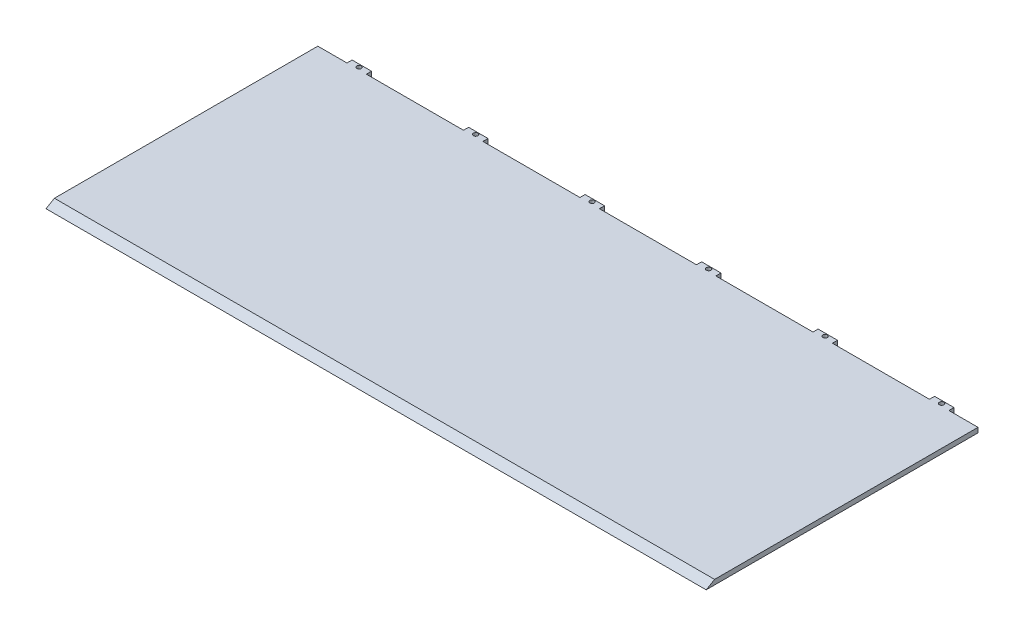
SolidWorks part; units mm, degrees
ref_plane "Front Plane" through (0, 0, 0) normal (0, 0, 1) x (1, 0, 0)
ref_plane "Top Plane" through (0, 0, 0) normal (0, 1, 0) x (1, 0, 0)
ref_plane "Right Plane" through (0, 0, 0) normal (1, 0, 0) x (0, 0, -1)
sketch "Sketch1" plane through (0, 0, 0) normal (0, 1, 0) x (1, 0, 0)
  line L1 (0, 0) -> (431.8, 0)
  line L2 (0, 0) -> (0, 177.8)
  line L3 (0, 177.8) -> (431.8, 177.8)
  line L4 (431.8, 0) -> (431.8, 177.8)
  dimension "D1" = 431.8
  dimension "D2" = 177.8
extrude "Boss-Extrude1" add sketch "Sketch1" along normal blind 3.175
sketch "Sketch2" plane through (0, 3.175, 0) normal (0, 1, 0) x (1, 0, 0)
  line L0 (431.8, 177.8) -> (0, 177.8) construction
  line L1 (19.05, 177.8) -> (31.75, 177.8)
  line L2 (19.05, 177.8) -> (19.05, 181.1655)
  line L3 (19.05, 181.1655) -> (31.75, 181.1655)
  line L4 (31.75, 177.8) -> (31.75, 181.1655)
  line L5 (0, 177.8) -> (0, 0) construction
  dimension "D1" = 12.7
  dimension "D2" = 3.3655
  dimension "D3" = 19.05
extrude "Boss-Extrude2" add sketch "Sketch2" against normal blind 3.175
hole_wizard "#32 (0.116) Diameter Hole1" positions "Sketch5" profile "Sketch4" hole size "#32" standard "ANSI Inch" end condition through all
sketch "Sketch5" plane through (0, 3.175, 0) normal (0, 1, 0) x (1, 0, 0)
  line L0 (31.75, 181.1655) -> (19.05, 181.1655) construction
  point P0 (25.4153, 179.3875)
  dimension "D1" = 1.778
sketch "Sketch4" plane through (25.4153, 3.175, -179.3875) normal (1, 0, 0) x (0, 0, 1)
  line L0 (0, 0) -> (0, 3.175)
  line L1 (0, 3.175) -> (1.4732, 3.175)
  line L2 (1.4732, 3.175) -> (1.4732, 0)
  line L5 (1.4732, 0) -> (0, 0)
  line L11 (0, -6.35) -> (0, 107.95) construction
  dimension "Thru Hole Dia." = 2.9464
  dimension "Thru Hole Depth" = 3.1751
pattern_linear "LPattern1" count 6 spacing 76.2 along (1, 0, 0) of "#32 (0.116) Diameter Hole1", "Boss-Extrude2"
sketch "Sketch6" plane through (0, 0, 0) normal (-1, 0, 0) x (0, 0, 1)
  line L0 (0, 0) -> (-5.4993, 3.175)
  line L1 (-177.8, 3.175) -> (0, 3.175) construction
  line L2 (0, 3.175) -> (0, 0) construction
  dimension "D1" = 60
extrude "Cut-Extrude1" cut sketch "Sketch6" against normal through all and the other way through all flip side to cut
